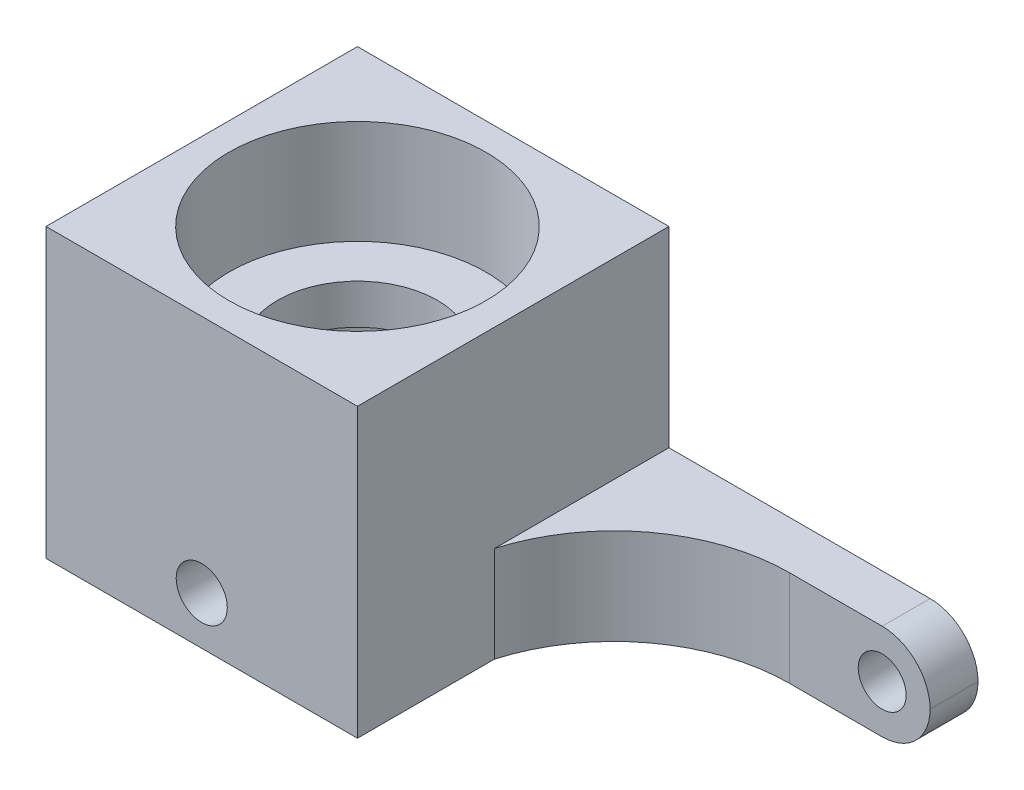
SolidWorks part; units mm, degrees
note: The reader was unsure of these and kept them because the rebuilt part matched: shared geometry of "Sketch4<5>", "Sketch4<8>", "Sketch1<4>", "Sketch1<6>", "Sketch1<8>".
material "PLA"
ref_plane "Front Plane" through (0, 0, 0) normal (0, 0, 1) x (1, 0, 0)
ref_plane "Top Plane" through (0, 0, 0) normal (0, 1, 0) x (1, 0, 0)
ref_plane "Right Plane" through (0, 0, 0) normal (1, 0, 0) x (0, 0, -1)
sketch "Sketch1" plane through (0, 0, 0) normal (0, 1, 0) x (1, 0, 0)
  circle A1 centre (0, 0) radius 8.05
  circle A2 centre (0, 0) radius 7.5
  circle A3 centre (0, 0) radius 9.75
  circle A6 centre (0, 0) radius 5
  point P6 (0, 0)
  dimension "D2" = 16.1
  dimension "D3" = 15
  dimension "D4" = 19.5
  dimension "D8" = 10
extrude "Boss-Extrude1" add sketch "Sketch1" along normal blind 18 contours A3
ref_plane "Plane2" through (0, 0, -9.75) normal (0, 0, -1) x (-1, 0, 0)
sketch "Sketch4" plane through (0, 0, -9.75) normal (0, 0, -1) x (-1, 0, 0)
  line L0 (-9.75, 18) -> (-9.75, 6)
  line L1 (9.75, 0) -> (-9.75, 0) construction
  line L2 (9.75, 18) -> (-9.75, 18) construction
  line L3 (0, 0) -> (0, 1.4)
  line L6 (9.75, 18) -> (-9.75, 18)
  line L8 (-9.75, 6) -> (9.75, 6) construction
  line L9 (-9.75, 6) -> (9.75, 0) construction
  line L10 (9.75, 6) -> (-9.75, 0) construction
  line L11 (-29.1, 0) -> (-9.75, 0)
  line L12 (-29.1, 0) -> (-29.1, 6)
  line L13 (-29.1, 6) -> (-9.75, 6)
  line L14 (-29.1, 3) -> (0, 3) construction
  line L15 (-9.75, 0) -> (9.75, 0)
  line L16 (-26.1, 0) -> (-26.1, 6)
  line L17 (9.75, 18) -> (9.75, 0)
  line L18 (0, 4.6) -> (0, 18)
  line L19 (-9.75, 6) -> (-9.75, 0)
  circle A0 centre (0, 3) radius 1.6
  circle A1 centre (-26.1, 3) radius 1.5
  point P17 (-29.1, 3)
  dimension "D2" = 3.2
  dimension "D5" = 26.1
  dimension "D6" = 3
  dimension "D3" = 6
  dimension "D4" = 3
extrude "Boss-Extrude3" add sketch "Sketch4<5>" against normal blind 3
sketch "Sketch4<5>" plane through (0, 0, -9.75) normal (0, 0, -1) x (-1, 0, 0) same geometry as "Sketch4"
extrude "Boss-Extrude5" add sketch "Sketch4<8>" against normal up to body separate body contours A0 L18 L6 L0 L19 L15 L3 | A0 L3 L15 L17 L6 L18
sketch "Sketch4<8>" plane through (0, 0, -9.75) normal (0, 0, -1) x (-1, 0, 0) same geometry as "Sketch4"
extrude "Cut-Extrude2" cut sketch "Sketch1<4>" along normal blind 9 contours A2
sketch "Sketch1<4>" plane through (0, 0, 0) normal (0, 1, 0) x (1, 0, 0) same geometry as "Sketch1"
extrude "Cut-Extrude8" cut sketch "Sketch1<6>" against normal blind 6.5 from surface at 18
sketch "Sketch1<6>" plane through (0, 0, 0) normal (0, 1, 0) x (1, 0, 0) same geometry as "Sketch1"
extrude "Cut-Extrude5" cut sketch "Sketch4" against normal through all both and the other way through all contours A0
fillet "Fillet8" radius 11 1 edges at (9.75, 3, -6.75)
fillet "Fillet9" radius 3 2 edges at (29.1, 0, -8.25) (29.1, 6, -8.25)
extrude "Cut-Extrude9" cut sketch "Sketch1<8>" against normal blind 4 from surface at 11.5 starting at face at (0, 11.5, 8.05)
sketch "Sketch1<8>" plane through (0, 0, 0) normal (0, 1, 0) x (1, 0, 0) same geometry as "Sketch1"
ref_plane "Plane3" through (0, 0, 9.75) normal (0, 0, 1) x (1, 0, 0)
sketch "Sketch5" plane through (0, 0, 9.75) normal (0, 0, 1) x (1, 0, 0)
  line L0 (9.75, 0) -> (-9.75, 0) construction
  line L1 (9.75, 6) -> (9.75, 0) construction
  line L2 (9.75, 18) -> (9.75, 6) construction
  line L3 (-9.75, 18) -> (9.75, 18) construction
  line L4 (-9.75, 18) -> (-9.75, 0) construction
  line L5 (9.75, 0) -> (-9.75, 0)
  line L6 (9.75, 6) -> (9.75, 0)
  line L7 (9.75, 18) -> (9.75, 6)
  line L8 (-9.75, 18) -> (9.75, 18)
  line L9 (-9.75, 18) -> (-9.75, 0)
  circle A0 centre (0, 3) radius 1.6 construction
  circle A1 centre (0, 3) radius 1.6
extrude "Boss-Extrude6" add sketch "Sketch5" against normal up to surface (9.75 mm away)
